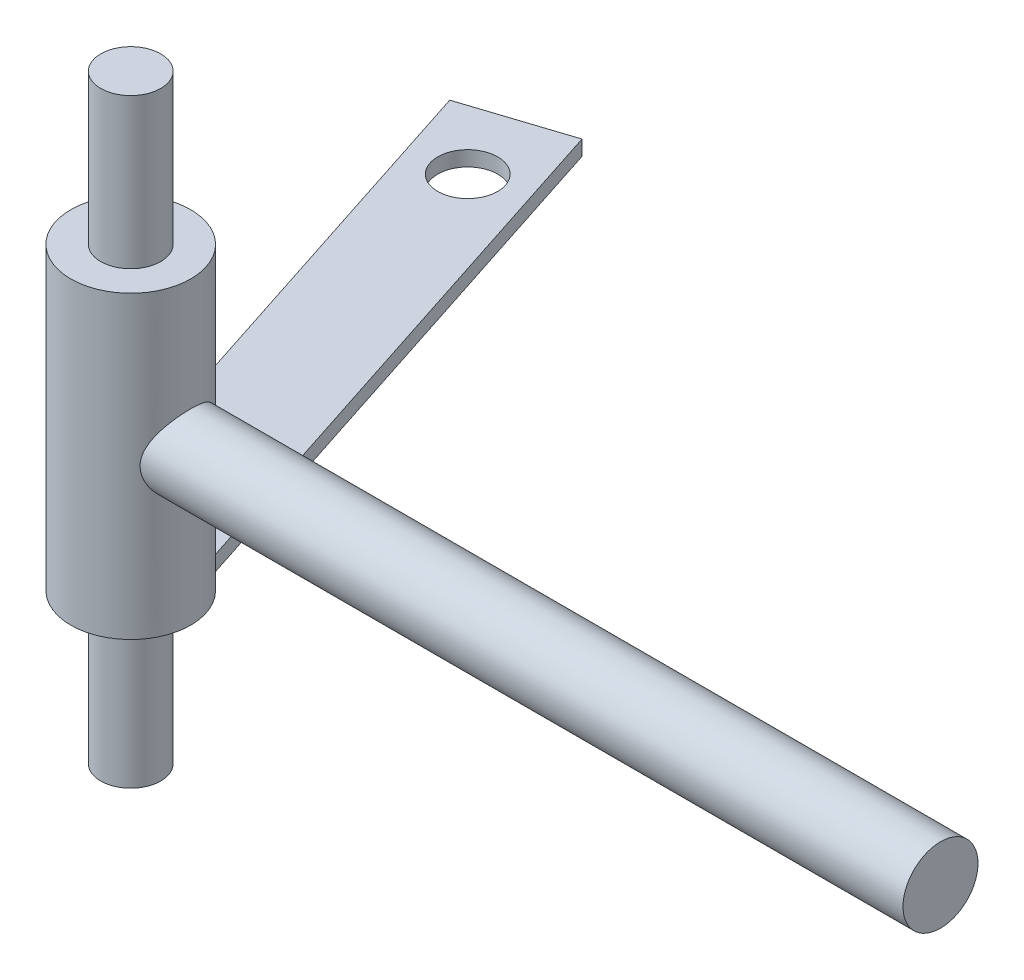
SolidWorks part; units mm, degrees
ref_plane "Front Plane" through (0, 0, 0) normal (0, 0, 1) x (1, 0, 0)
ref_plane "Top Plane" through (0, 0, 0) normal (0, 1, 0) x (1, 0, 0)
ref_plane "Right Plane" through (0, 0, 0) normal (1, 0, 0) x (0, 0, -1)
sketch "Sketch1" plane through (0, 0, 0) normal (0, 1, 0) x (1, 0, 0)
  circle A0 centre (0, 0) radius 4
  dimension "D1" = 8
extrude "Boss-Extrude1" add sketch "Sketch1" along normal mid plane 80
ref_axis "Axis2" through (0, 40, 0) along (0, -1, 0)
ref_plane "Plane1" through (0, 0, 0) normal (0.309, 0, 0.9511) x (0, -1, 0)
sketch "Sketch3" plane through (0, 0, 0) normal (0, 1, 0) x (1, 0, 0)
  circle A0 centre (0, 0) radius 8
  dimension "D1" = 16
extrude "Boss-Extrude2" add sketch "Sketch3" along normal mid plane 40
sketch "Sketch4" plane through (0, 0, 0) normal (1, 0, 0) x (0, 0, -1)
  circle A0 centre (0, 0) radius 5
  dimension "D1" = 10
extrude "Boss-Extrude3" add sketch "Sketch4" along normal blind 108
sketch "Sketch5" plane through (0, 0, 0) normal (0.309, 0, 0.9511) x (0.9511, 0, -0.309)
  line L0 (-8, -20) -> (8, -20) construction
  line L5 (-7, -16) -> (7, -16)
  line L6 (-7, -16) -> (-7, -18)
  line L7 (-7, -18) -> (7, -18)
  line L8 (7, -16) -> (7, -18)
  line L9 (-7, -16) -> (7, -18) construction
  line L10 (-7, -18) -> (7, -16) construction
  point P0 (0, -17)
  dimension "D1" = 14
  dimension "D2" = 2
  dimension "D3" = 2
extrude "Boss-Extrude4" add sketch "Sketch5" against normal blind 80
sketch "Sketch6" plane through (0, -16, 0) normal (0, 1, 0) x (1, 0, 0)
  line L1 (-18.064, 78.2476) -> (-31.3788, 73.9214) construction
  line L2 (-31.3788, 73.9214) -> (-7.8542, 1.5203) construction
  circle A0 centre (-21.6312, 66.574) radius 4
  dimension "D1" = 8
  dimension "D2" = 10
  dimension "D3" = 7
extrude "Cut-Extrude1" cut sketch "Sketch6" against normal up to next
ref_axis "Axis1" through (108, 0, 0) along (-1, 0, 0)
